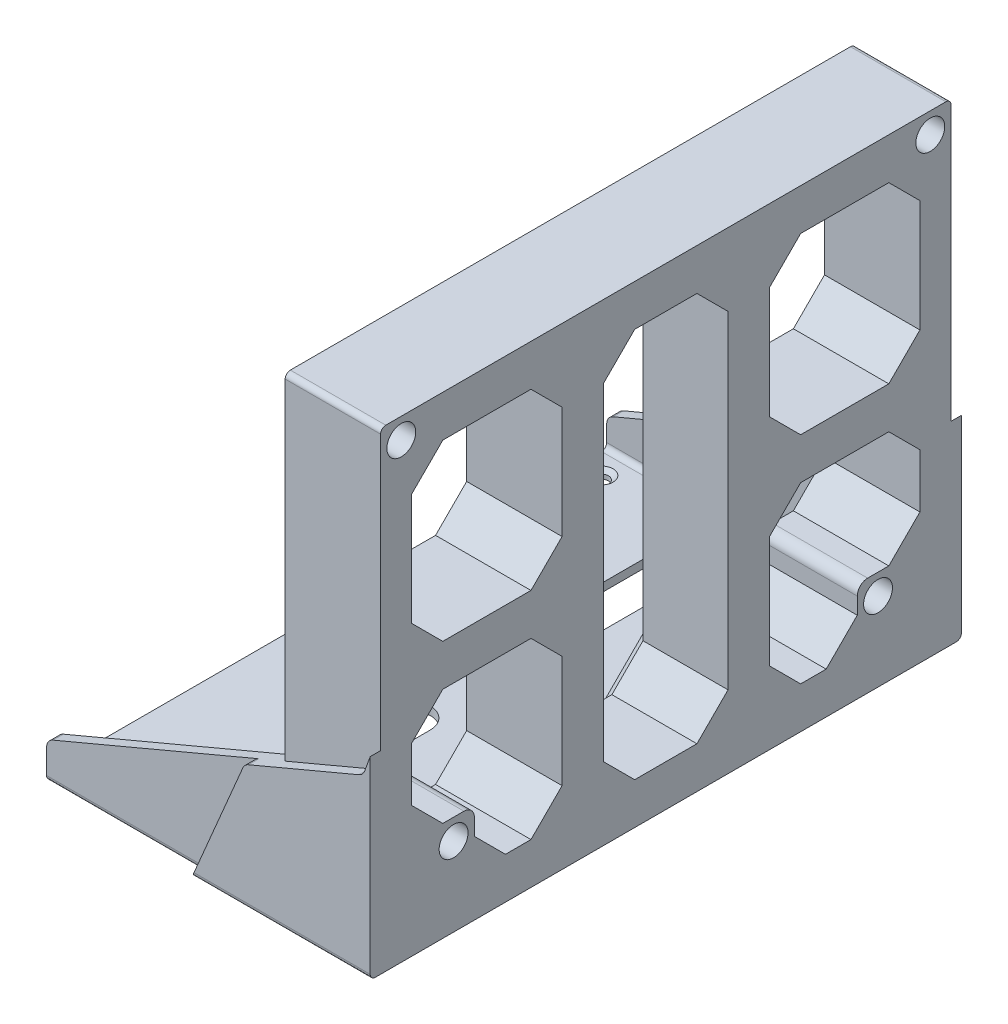
SolidWorks part; units mm, degrees
material "Nylon 101"
ref_plane "Front Plane" through (0, 0, 0) normal (0, 0, 1) x (1, 0, 0)
ref_plane "Top Plane" through (0, 0, 0) normal (0, 1, 0) x (1, 0, 0)
ref_plane "Right Plane" through (0, 0, 0) normal (1, 0, 0) x (0, 0, -1)
sketch "Sketch2" plane through (149.225, 0, 0) normal (1, 0, 0) x (0, 0, -1)
  line L8 (-6.477, 0) -> (-6.477, -144.78)
  line L9 (-6.477, -144.78) -> (174.498, -144.78)
  line L10 (174.498, -144.78) -> (174.498, 0)
  line L11 (174.498, 0) -> (-6.477, 0)
extrude "Boss-Extrude1" add sketch "Sketch2" against normal up to surface (149.225 mm away)
sketch "Sketch3" plane through (0, 0, 6.477) normal (0, 0, 1) x (1, 0, 0)
  line L0 (60.325, 0) -> (0, 0)
  line L1 (0, 0) -> (0, -102.8733)
  line L2 (0, -144.78) -> (0, 0) construction
  line L12 (-9.2712, -106.7829) -> (-25.4, -144.78)
  line L13 (-25.4, -144.78) -> (149.225, -144.78)
  line L14 (149.225, -144.78) -> (149.225, 0)
  line L15 (149.225, 0) -> (60.325, 0)
  line L16 (60.325, 0) -> (27.031, -91.4744)
  line L17 (27.031, -91.4744) -> (-9.2712, -106.7829)
extrude "Boss-Extrude2" add sketch "Sketch3<3>" against normal blind 3.175 contours L16 L17 L12 L13 L14 L15
sketch "Sketch3<3>" plane through (0, 0, 6.477) normal (0, 0, 1) x (1, 0, 0) same geometry as "Sketch3"
sketch "Sketch4" plane through (0, 0, 0.127) normal (0, 0, 1) x (1, 0, 0)
  line L8 (-73.025, -133.6675) -> (-73.025, -144.78)
  line L9 (-73.025, -144.78) -> (-25.4, -144.78)
  line L10 (-25.4, -144.78) -> (-9.2712, -106.7829)
  line L11 (-9.2712, -106.7829) -> (-73.025, -133.6675)
extrude "Boss-Extrude3" add sketch "Sketch4" along normal blind 3.175
sketch "Sketch5" plane through (0, 0, 3.302) normal (0, 0, -1) x (-1, 0, 0)
  line L4 (0, -102.8733) -> (0, -144.78)
  line L5 (0, -144.78) -> (25.4, -144.78)
  line L6 (25.4, -144.78) -> (9.2712, -106.7829)
  line L7 (9.2712, -106.7829) -> (0, -102.8733)
  line L8 (0, -102.8733) -> (0, -144.78)
  line L9 (0, -144.78) -> (25.4, -144.78)
  line L10 (25.4, -144.78) -> (9.2712, -106.7829)
  line L11 (9.2712, -106.7829) -> (0, -102.8733)
  dimension "D1" = 0
extrude "Boss-Extrude4" add sketch "Sketch5" along normal blind 3.175
ref_plane "Plane1" through (0, 0, -84.0105) normal (0, 0, 1) x (1, 0, 0)
mirror "Mirror5" about plane through (0, 0, -84.0105) normal (0, 0, 1) of bodies 105 104
extrude "Cut-Extrude1" cut sketch "Sketch3" against normal blind 3.175 contours L0 L1 region at (22.3809, -41.9815, 6.477)
mirror "Mirror6" about plane through (0, 0, -84.0105) normal (0, 0, 1) of "Cut-Extrude1"
sketch "Sketch7" plane through (0, -144.78, 0) normal (0, -1, 0) x (1, 0, 0)
  line L1 (0, 0.127) -> (-73.025, 0.127)
  line L2 (0, 0.127) -> (0, -171.323)
  line L3 (0, -171.323) -> (-73.025, -171.323)
  line L4 (-73.025, 0.127) -> (-73.025, -171.323)
  line L5 (0, 0.127) -> (-73.025, -171.323) construction
  line L6 (0, -171.323) -> (-73.025, 0.127) construction
  line L8 (-73.025, 3.302) -> (-73.025, 0.127) construction
  line L10 (0, -168.148) -> (0, 0.127) construction
  point P4 (-36.5125, -85.598)
extrude "Boss-Extrude6" add sketch "Sketch7" against normal blind 2.54
fillet "Fillet1" radius 1.5875 2 edges at (30.1625, 0, -171.323) (30.1625, 0, 3.302)
sketch "Sketch10" plane through (149.225, 0, 0) normal (1, 0, 0) x (0, 0, -1)
  line L8 (161.798, -12.7) -> (6.223, -12.7)
  line L9 (6.223, -12.7) -> (6.223, -132.08)
  line L10 (6.223, -132.08) -> (161.798, -132.08)
  line L11 (161.798, -132.08) -> (161.798, -12.7)
  line L12 (161.798, -12.7) -> (6.223, -12.7)
  line L13 (6.223, -12.7) -> (6.223, -132.08)
  line L14 (6.223, -132.08) -> (161.798, -132.08)
  line L15 (161.798, -132.08) -> (161.798, -12.7)
  dimension "D1" = 12.7
extrude "Cut-Extrude2" cut sketch "Sketch10" against normal through all
fillet "Fillet3" radius 3.175 6 edges at (-73.025, -133.6675, -169.7355) (-9.2712, -106.7829, -172.9105) (27.031, -91.4744, -172.9105) (-9.2712, -106.7829, 4.8895) (-73.025, -133.6675, 1.7145) (27.031, -91.4744, 4.8895)
chamfer "Chamfer1" distance 6.35 angle 45 4 edges at (74.6125, -12.7, -6.223) (74.6125, -132.08, -6.223) (74.6125, -132.08, -161.798) (74.6125, -12.7, -161.798)
fillet "Fillet4" radius 6.35 8 edges at (74.6125, -132.08, -155.448) (74.6125, -132.08, -12.573) (74.6125, -125.73, -6.223) (74.6125, -19.05, -6.223) (74.6125, -12.7, -12.573) (74.6125, -12.7, -155.448) (74.6125, -19.05, -161.798) (74.6125, -125.73, -161.798)
sketch "Sketch11" plane through (149.225, 0, 0) normal (1, 0, 0) x (0, 0, -1)
  line L4 (174.498, 0) -> (-6.477, 0)
  line L5 (-6.477, 0) -> (-6.477, -144.78)
  line L6 (-6.477, -144.78) -> (174.498, -144.78)
  line L7 (174.498, -144.78) -> (174.498, 0)
  line L8 (174.498, 0) -> (-6.477, 0)
  line L9 (-6.477, 0) -> (-6.477, -144.78)
  line L10 (-6.477, -144.78) -> (174.498, -144.78)
  line L11 (174.498, -144.78) -> (174.498, 0)
  dimension "D1" = 0
extrude "Cut-Extrude3" cut sketch "Sketch11" against normal blind 82.55
fillet "Fillet5" radius 1.5875 6 edges at (-36.5125, -142.24, 0.127) (-36.5125, -142.24, -168.148) (-49.2125, -144.78, -171.323) (20.6375, -144.78, -174.498) (20.6375, -144.78, 6.477) (-49.2125, -144.78, 3.302) tangent propagation no
sketch "Sketch12" plane through (0, -144.78, 0) normal (0, -1, 0) x (1, 0, 0)
  line L2 (-38.1, -101.473) -> (-38.1, -152.273)
  line L3 (-38.1, -101.473) -> (-38.1, -152.273)
  line L4 (-25.4, -152.273) -> (-25.4, -101.473)
  line L5 (-25.4, -152.273) -> (-25.4, -101.473)
  line L37 (-25.4, -66.548) -> (-25.4, -15.748)
  line L38 (-38.1, -15.748) -> (-38.1, -66.548)
  line L39 (-25.4, -66.548) -> (-25.4, -15.748)
  line L40 (-38.1, -15.748) -> (-38.1, -66.548)
  arc A3 (-38.1, -152.273) -> (-25.4, -152.273) centre (-31.75, -152.273) ccw
  arc A4 (-38.1, -152.273) -> (-25.4, -152.273) centre (-31.75, -152.273) ccw
  arc A5 (-25.4, -101.473) -> (-38.1, -101.473) centre (-31.75, -101.473) ccw
  arc A6 (-25.4, -101.473) -> (-38.1, -101.473) centre (-31.75, -101.473) ccw
  arc A34 (-25.4, -15.748) -> (-38.1, -15.748) centre (-31.75, -15.748) ccw
  arc A35 (-38.1, -66.548) -> (-25.4, -66.548) centre (-31.75, -66.548) ccw
  arc A36 (-25.4, -15.748) -> (-38.1, -15.748) centre (-31.75, -15.748) ccw
  arc A37 (-38.1, -66.548) -> (-25.4, -66.548) centre (-31.75, -66.548) ccw
  dimension "D1" = 0
  dimension "D2" = 0
extrude "Cut-Extrude4" cut sketch "Sketch12" against normal up to next
sketch "Sketch18" plane through (66.675, 0, 0) normal (1, 0, 0) x (0, 0, -1)
  line L0 (162.7855, -114.3) -> (145.796, -114.3) construction
  line L1 (142.621, -117.475) -> (142.621, -130.175) construction
  line L2 (152.8177, -132.08) -> (15.2033, -132.08) construction
  line L3 (159.9381, -127.5899) -> (157.3079, -130.2201) construction
  line L4 (161.798, -21.6803) -> (161.798, -123.0997) construction
  line L5 (161.798, -114.3) -> (145.796, -114.3)
  line L6 (142.621, -117.475) -> (142.621, -132.08)
  line L7 (152.8177, -132.08) -> (142.621, -132.08)
  line L8 (159.9381, -127.5899) -> (157.3079, -130.2201)
  line L9 (161.798, -114.3) -> (161.798, -123.0997)
  line L10 (84.0105, -132.08) -> (84.0105, -72.39) construction
  line L11 (84.0105, -72.39) -> (6.223, -72.39) construction
  line L12 (6.223, -123.0997) -> (6.223, -21.6803) construction
  line L13 (6.223, -114.3) -> (6.223, -123.0997)
  line L14 (8.0829, -127.5899) -> (10.7131, -130.2201)
  line L15 (15.2033, -132.08) -> (25.4, -132.08)
  line L16 (25.4, -117.475) -> (25.4, -132.08)
  line L17 (6.223, -114.3) -> (22.225, -114.3)
  line L18 (6.223, -30.48) -> (22.225, -30.48)
  line L19 (25.4, -27.305) -> (25.4, -12.7)
  line L20 (15.2033, -12.7) -> (25.4, -12.7)
  line L21 (8.0829, -17.1901) -> (10.7131, -14.5599)
  line L22 (6.223, -30.48) -> (6.223, -21.6803)
  line L23 (161.798, -30.48) -> (161.798, -21.6803)
  line L24 (159.9381, -17.1901) -> (157.3079, -14.5599)
  line L25 (152.8177, -12.7) -> (142.621, -12.7)
  line L26 (142.621, -27.305) -> (142.621, -12.7)
  line L27 (161.798, -30.48) -> (145.796, -30.48)
  arc A0 (145.796, -114.3) -> (142.621, -117.475) centre (145.796, -117.475) ccw construction
  arc A1 (152.8177, -132.08) -> (157.3079, -130.2201) centre (152.8177, -125.73) ccw construction
  arc A2 (159.9381, -127.5899) -> (161.798, -123.0997) centre (155.448, -123.0997) ccw construction
  arc A3 (145.796, -114.3) -> (142.621, -117.475) centre (145.796, -117.475) ccw
  arc A4 (152.8177, -132.08) -> (157.3079, -130.2201) centre (152.8177, -125.73) ccw
  arc A5 (159.9381, -127.5899) -> (161.798, -123.0997) centre (155.448, -123.0997) ccw
  arc A6 (8.0829, -127.5899) -> (6.223, -123.0997) centre (12.573, -123.0997) cw
  arc A7 (15.2033, -132.08) -> (10.7131, -130.2201) centre (15.2033, -125.73) cw
  arc A8 (22.225, -114.3) -> (25.4, -117.475) centre (22.225, -117.475) cw
  arc A9 (22.225, -30.48) -> (25.4, -27.305) centre (22.225, -27.305) ccw
  arc A10 (15.2033, -12.7) -> (10.7131, -14.5599) centre (15.2033, -19.05) ccw
  arc A11 (8.0829, -17.1901) -> (6.223, -21.6803) centre (12.573, -21.6803) ccw
  arc A12 (159.9381, -17.1901) -> (161.798, -21.6803) centre (155.448, -21.6803) cw
  arc A13 (152.8177, -12.7) -> (157.3079, -14.5599) centre (152.8177, -19.05) cw
  arc A14 (145.796, -30.48) -> (142.621, -27.305) centre (145.796, -27.305) cw
  line M12 (15.2033, -12.7) -> (152.8177, -12.7)
  arc M13 (152.8177, -12.7) -> (157.3079, -14.5599) centre (152.8177, -19.05) cw
  line M14 (157.3079, -14.5599) -> (159.9381, -17.1901)
  arc M15 (159.9381, -17.1901) -> (161.798, -21.6803) centre (155.448, -21.6803) cw
  line M16 (161.798, -21.6803) -> (161.798, -123.0997)
  arc M17 (161.798, -123.0997) -> (159.9381, -127.5899) centre (155.448, -123.0997) cw
  line M18 (159.9381, -127.5899) -> (157.3079, -130.2201)
  arc M19 (157.3079, -130.2201) -> (152.8177, -132.08) centre (152.8177, -125.73) cw
  line M20 (152.8177, -132.08) -> (15.2033, -132.08)
  arc M21 (15.2033, -132.08) -> (10.7131, -130.2201) centre (15.2033, -125.73) cw
  line M22 (10.7131, -130.2201) -> (8.0829, -127.5899)
  arc M23 (8.0829, -127.5899) -> (6.223, -123.0997) centre (12.573, -123.0997) cw
  line M24 (6.223, -123.0997) -> (6.223, -21.6803)
extrude "Boss-Extrude7" add sketch "Sketch18" against normal up to surface (66.675 mm away) contours A8 L17 L16 M24 M23 M22 M21 M20 | L5 A3 L6 M20 M19 M18 M17 M16 region at (66.675, -122.7851, -151.7611) region at (66.675, -122.7851, -16.2599) up to face at (0, -72.39, -84.0105)
extrude "Boss-Extrude8" add sketch "Sketch18<3>" against normal blind 9.525 contours A14 L27 L26 M16 M15 M14 M13 M12 | L19 L20 A10 L21 A11 L22 L18 A9 region at (66.675, -21.9949, -151.7611)
sketch "Sketch18<3>" plane through (66.675, 0, 0) normal (1, 0, 0) x (0, 0, -1) same geometry as "Sketch18"
hole_wizard "S (0.348) Diameter Hole1" positions "Sketch9" profile "Sketch8" hole size "S" standard "ANSI Inch" end condition through all
sketch "Sketch9" plane through (0, 0, 0) normal (-1, 0, 0) x (0, 0, 1)
  point P0 (-164.973, -6.35)
  point P3 (-3.048, -6.35)
  point P6 (-19.05, -120.65)
  point P9 (-148.971, -120.65)
sketch "Sketch8" plane through (0, -6.35, -164.973) normal (0, 1, 0) x (0, 0, 1)
  line L0 (0, 0) -> (0, 66.675)
  line L1 (0, 66.675) -> (4.4196, 66.675)
  line L2 (4.4196, 66.675) -> (4.4196, 0)
  line L5 (4.4196, 0) -> (0, 0)
  line L11 (0, -6.35) -> (0, 107.95) construction
  dimension "Thru Hole Dia." = 8.8392
  dimension "Thru Hole Depth" = 66.675
hole_wizard "CSK for #6 Flat Head Machine Screw (100)1" positions "Sketch16" profile "Sketch17" countersink size "#6" standard "ANSI Inch" end condition through all
sketch "Sketch16" plane through (0, -142.24, 0) normal (0, 1, 0) x (1, 0, 0)
  line L0 (-73.025, -1.7145) -> (-73.025, 169.7355) construction
  line L1 (-11.1125, 51.0043) -> (-11.1125, 2.7167) construction
  line L2 (-18.7187, -4.8895) -> (-40.6538, -4.8895) construction
  line L3 (-6.35, 84.0105) -> (-139.7, 84.0105) construction
  line L4 (-6.35, -8.8582) -> (-6.35, 176.8792) construction
  line L7 (-20.6375, 160.2105) -> (-66.675, 7.8105) construction
  point P0 (-20.6375, 7.8105)
  point P2 (-66.675, 7.8105)
  point P20 (-66.675, 160.2105)
  point P21 (-20.6375, 160.2105)
  point P26 (-43.6562, 84.0105)
  dimension "D1" = 6.35
  dimension "D2" = 9.525
  dimension "D3" = 12.7
sketch "Sketch17" plane through (-20.6375, -142.24, -7.8105) normal (1, 0, 0) x (0, 0, 1)
  line L0 (0, 0) -> (0, 2.54)
  line L1 (0, 2.54) -> (2.1526, 2.54)
  line L2 (2.1526, 2.54) -> (2.1526, 1.1669)
  line L3 (2.1526, 1.1669) -> (3.5433, 0)
  line L5 (3.5433, 0) -> (0, 0)
  line L6 (-2.1526, 1.1669) -> (-3.5433, 0) construction
  line L11 (0, -6.35) -> (0, 107.95) construction
  dimension "Thru Hole Dia." = 4.3053
  dimension "Thru Hole Depth" = 2.54
  dimension "Near C'Sink Dia." = 7.0866
  dimension "Near C'Sink Angle" = 100
hole_wizard "1/4 Clearance Hole1" positions "Sketch20" profile "Sketch21" hole size "1/4" standard "ANSI Inch" end condition through all
sketch "Sketch20" plane through (57.15, 0, 0) normal (-1, 0, 0) x (0, 0, 1)
  line L0 (-6.223, -30.48) -> (-22.225, -30.48) construction
  line L1 (-25.4, -27.305) -> (-25.4, -12.7) construction
  line L2 (-84.0105, -12.7) -> (-84.0105, -132.08) construction
  line L3 (-25.4, -12.7) -> (-142.621, -12.7) construction
  line L4 (-142.621, -132.08) -> (-25.4, -132.08) construction
  point P0 (-19.05, -24.13)
  point P16 (-148.971, -24.13)
  dimension "D1" = 6.35
  dimension "D2" = 6.35
sketch "Sketch21" plane through (57.15, -24.13, -19.05) normal (0, 1, 0) x (0, 0, 1)
  line L0 (0, 0) -> (0, 9.525)
  line L1 (0, 9.525) -> (3.5712, 9.525)
  line L2 (3.5712, 9.525) -> (3.5712, 0)
  line L5 (3.5712, 0) -> (0, 0)
  line L11 (0, -6.35) -> (0, 107.95) construction
  dimension "Thru Hole Dia." = 7.1425
  dimension "Thru Hole Depth" = 9.525
sketch "Sketch22" plane through (66.675, 0, 0) normal (1, 0, 0) x (0, 0, -1)
  line L4 (-4.8895, -144.78) -> (172.9105, -144.78)
  line L5 (174.498, -143.1925) -> (174.498, 0)
  line L6 (174.498, 0) -> (-6.477, 0)
  line L7 (-6.477, 0) -> (-6.477, -143.1925)
  line L8 (-4.8895, -144.78) -> (172.9105, -144.78)
  line L9 (174.498, -143.1925) -> (174.498, 0)
  line L10 (174.498, 0) -> (-6.477, 0)
  line L11 (-6.477, 0) -> (-6.477, -143.1925)
  arc A2 (172.9105, -144.78) -> (174.498, -143.1925) centre (172.9105, -143.1925) ccw
  arc A3 (-6.477, -143.1925) -> (-4.8895, -144.78) centre (-4.8895, -143.1925) ccw
  arc A4 (172.9105, -144.78) -> (174.498, -143.1925) centre (172.9105, -143.1925) ccw
  arc A5 (-6.477, -143.1925) -> (-4.8895, -144.78) centre (-4.8895, -143.1925) ccw
  dimension "D1" = 0
extrude "Relief for MIP face support" cut sketch "Sketch22" against normal offset from surface (37.465 mm away) 102.235 up to face at (-73.025, -140.5119, -84.0105)
sketch "Sketch23" plane through (29.21, 0, 0) normal (1, 0, 0) x (0, 0, -1)
  line L0 (84.0105, -132.08) -> (84.0105, -12.7)
  line L1 (142.621, -132.08) -> (25.4, -132.08) construction
  line L2 (15.2033, -12.7) -> (152.8177, -12.7) construction
  line L3 (161.798, -67.9901) -> (6.223, -67.9901)
  line L4 (161.798, -21.6803) -> (161.798, -114.3) construction
  line L5 (6.223, -114.3) -> (6.223, -21.6803) construction
extrude "Extrude-Thin1" add sketch "Sketch23" against normal up to surface (29.21 mm away) thin up to face at (0, -6.35, -160.5534) thin type mid plane wall 6.35
fillet "Fillet6" radius 6.35 12 edges at (14.605, -12.7, -80.8355) (14.605, -12.7, -87.1855) (14.605, -64.8151, -161.798) (14.605, -71.1651, -161.798) (14.605, -132.08, -87.1855) (14.605, -132.08, -80.8355) (14.605, -71.1651, -80.8355) (14.605, -71.1651, -87.1855) (14.605, -64.8151, -6.223) (14.605, -71.1651, -6.223) (14.605, -64.8151, -80.8355) (14.605, -64.8151, -87.1855)
sketch "Sketch24" plane through (29.21, 0, 0) normal (1, 0, 0) x (0, 0, -1)
  line L0 (22.225, -114.3) -> (6.223, -114.3) construction
  line L1 (25.4, -132.08) -> (25.4, -114.3)
  line L2 (25.4, -114.3) -> (6.223, -114.3)
  line L3 (6.223, -114.3) -> (6.223, -12.7)
  line L4 (6.223, -12.7) -> (161.798, -12.7)
  line L5 (15.2033, -12.7) -> (74.4855, -12.7) construction
  line L6 (84.0105, 0) -> (84.0105, -144.78) construction
  line L7 (-1.7145, 0) -> (169.7355, 0) construction
  line L8 (172.9105, -144.78) -> (-4.8895, -144.78) construction
  line L9 (25.4, -132.08) -> (142.621, -132.08)
  line L10 (161.798, -114.3) -> (161.798, -12.7)
  line L11 (142.621, -114.3) -> (161.798, -114.3)
  line L12 (142.621, -132.08) -> (142.621, -114.3)
  point P19 (84.0105, -132.08)
  point P21 (84.0105, -12.7)
extrude "Cut-Extrude5" cut sketch "Sketch24" against normal up to surface (29.21 mm away) up to face at (0, -34.5124, -37.0344)
sketch "Sketch25" plane through (29.21, 0, 0) normal (1, 0, 0) x (0, 0, -1)
  line L0 (84.0105, -132.08) -> (84.0105, -12.7) construction
  line L1 (142.621, -132.08) -> (25.4, -132.08) construction
  line L2 (6.223, -12.7) -> (161.798, -12.7) construction
  line L3 (58.6105, -132.08) -> (58.6105, -12.7)
  line L4 (58.6105, -72.39) -> (6.223, -72.39)
  line L5 (6.223, -114.3) -> (6.223, -12.7) construction
  line L6 (109.4105, -72.39) -> (161.798, -72.39)
  line L7 (109.4105, -132.08) -> (109.4105, -12.7)
  dimension "D1" = 25.4
extrude "Extrude-Thin2" add sketch "Sketch25" against normal up to surface (29.21 mm away) thin up to face at (0, -98.0395, -84.0105) thin type mid plane wall 12.7
chamfer "Chamfer2" distance 9.525 angle 45 22 edges at (14.605, -132.08, -25.4) (14.605, -114.3, -6.223) (14.605, -78.74, -6.223) (14.605, -78.74, -52.2605) (14.605, -132.08, -52.2605) (14.605, -66.04, -52.2605) (14.605, -66.04, -6.223) (14.605, -12.7, -6.223) (14.605, -12.7, -52.2605) (14.605, -12.7, -103.0605) (14.605, -12.7, -64.9605) (14.605, -132.08, -64.9605) (14.605, -132.08, -103.0605) (14.605, -132.08, -115.7605) (14.605, -132.08, -142.621) (14.605, -114.3, -161.798) (14.605, -78.74, -161.798) (14.605, -78.74, -115.7605) (14.605, -66.04, -115.7605) (14.605, -66.04, -161.798) (14.605, -12.7, -161.798) (14.605, -12.7, -115.7605)
chamfer "Chamfer3" distance 3.175 angle 45 8 edges at (0, -127.3175, -69.723) (0, -72.39, -64.9605) (0, -17.4625, -69.723) (0, -12.7, -84.0105) (0, -17.4625, -98.298) (0, -72.39, -103.0605) (0, -127.3175, -98.298) (0, -132.08, -84.0105)
